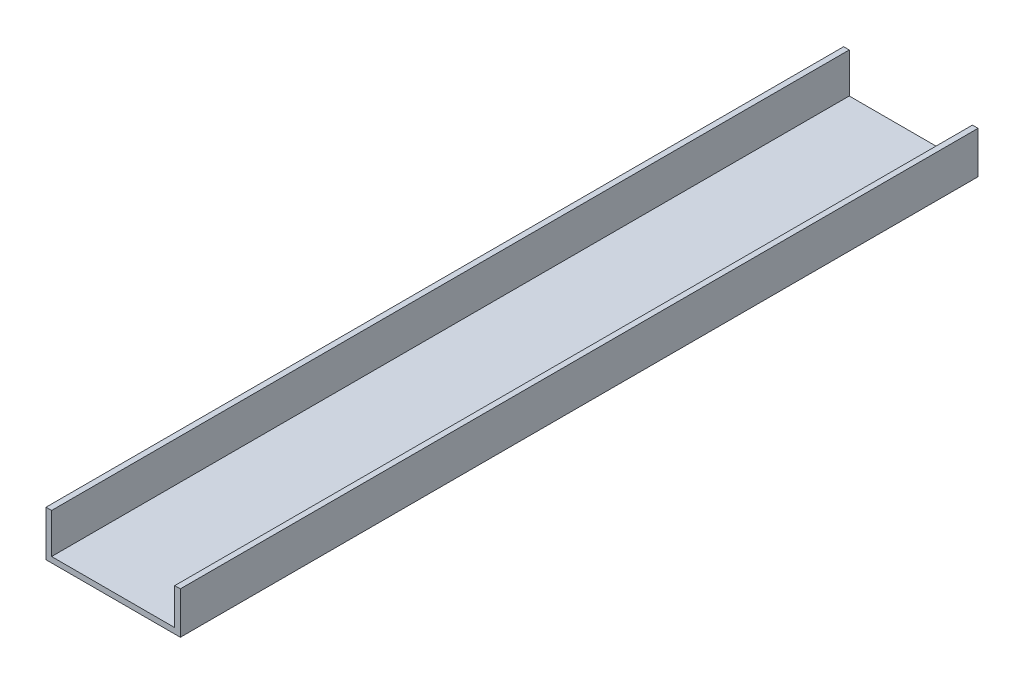
SolidWorks part; units mm, degrees
material "Corrugated Paper"
ref_plane "Front Plane" through (0, 0, 0) normal (0, 0, 1) x (1, 0, 0)
ref_plane "Top Plane" through (0, 0, 0) normal (0, 1, 0) x (1, 0, 0)
ref_plane "Right Plane" through (0, 0, 0) normal (1, 0, 0) x (0, 0, -1)
sketch "Sketch1" plane through (0, 0, 0) normal (0, 0, 1) x (1, 0, 0)
  line L0 (0, 0) -> (48, 0)
  line L1 (48, 0) -> (48, 15)
  line L2 (0, 0) -> (0, 16.2604)
  dimension "D1" = 48
  dimension "D2" = 15
extrude "Extrude-Thin1" add sketch "Sketch1" along normal blind 285 thin thin type one direction wall 2
